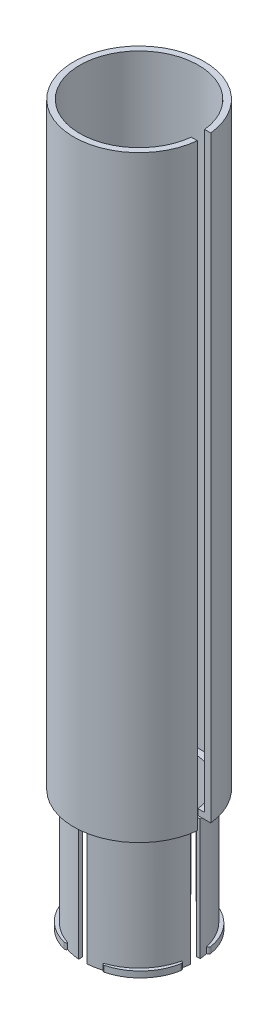
SolidWorks part; units mm, degrees
ref_plane "Front Plane" through (0, 0, 0) normal (0, 0, 1) x (1, 0, 0)
ref_plane "Top Plane" through (0, 0, 0) normal (0, 1, 0) x (1, 0, 0)
ref_plane "Right Plane" through (0, 0, 0) normal (1, 0, 0) x (0, 0, -1)
sketch "Sketch1" plane through (0, 0, 0) normal (0, 1, 0) x (1, 0, 0)
  line L5 (15.2664, 15.2664) -> (-15.2664, -15.2664) construction
  line L6 (15.2664, -15.2664) -> (-15.2664, 15.2664) construction
  circle A0 centre (0, 0) radius 21.59
  point P0 (0, 0)
  dimension "D1" = 43.18
extrude "Boss-Extrude1" add sketch "Sketch1" along normal blind 200
shell "Shell1" thickness 2
sketch "Sketch2" plane through (0, 0, 0) normal (1, 0, 0) x (0, 0, -1)
  line L0 (0, 19.558) -> (0, -19.558) construction
  line L2 (2.214, 104.2698) -> (2.214, 0)
  line L3 (2.214, 0) -> (-2.214, 0)
  line L4 (-2.214, 104.2698) -> (-2.214, 0)
  line L5 (2.214, 104.2698) -> (-2.214, 0) construction
  line L6 (2.214, 0) -> (-2.214, 104.2698) construction
  line L7 (19.558, 0) -> (-19.558, 0) construction
  line L10 (-2.214, 104.2698) -> (-2.214, 199.7944)
  line L11 (-2.214, 199.7944) -> (2.214, 199.7944)
  line L12 (2.214, 104.2698) -> (2.214, 199.7944)
  point P0 (0, 52.1349)
extrude "Cut-Extrude1" cut sketch "Sketch2" against normal mid plane 10 from offset 20
sketch "Sketch4" plane through (0, 0, 0) normal (0, -1, 0) x (1, 0, 0)
  circle A0 centre (0, 0) radius 18.651
extrude "Boss-Extrude2" add sketch "Sketch4" along normal blind 40
sketch "Sketch7" plane through (0, -40, 0) normal (0, -1, 0) x (-1, 0, 0)
  circle A0 centre (0, 0) radius 17.4097
extrude "Cut-Extrude4" cut sketch "Sketch7" against normal blind 62
sketch "Sketch8" plane through (0, 0, 0) normal (0, 1, 0) x (1, 0, 0)
  line L0 (0, -19.558) -> (0, 19.558) construction
  line L1 (-1.3929, 23.0464) -> (1.3929, 23.0464)
  line L2 (-1.3929, 23.0464) -> (-1.3929, 17.1698)
  line L3 (-1.3929, 17.1698) -> (1.3929, 17.1698)
  line L4 (1.3929, 23.0464) -> (1.3929, 17.1698)
  line L5 (-1.3929, 23.0464) -> (1.3929, 17.1698) construction
  line L6 (-1.3929, 17.1698) -> (1.3929, 23.0464) construction
  line L7 (14.2708, 1.6027) -> (23.1489, 1.6027)
  line L8 (14.2708, 1.6027) -> (14.2708, -1.6047)
  line L9 (14.2708, -1.6047) -> (23.1489, -1.6047)
  line L10 (23.1489, 1.6027) -> (23.1489, -1.6047)
  line L11 (14.2708, 1.6027) -> (23.1489, -1.6047) construction
  line L12 (14.2708, -1.6047) -> (23.1489, 1.6027) construction
  line L13 (-1.3657, -14.1994) -> (1.3929, -14.1994)
  line L14 (-1.3657, -14.1994) -> (-1.3657, -22.705)
  line L15 (-1.3657, -22.705) -> (1.3929, -22.705)
  line L16 (1.3929, -14.1994) -> (1.3929, -22.705)
  line L17 (-1.3657, -14.1994) -> (1.3929, -22.705) construction
  line L18 (-1.3657, -22.705) -> (1.3929, -14.1994) construction
  line L19 (-14.2708, 1.6027) -> (-23.1489, 1.6027)
  line L20 (-23.1489, 1.6027) -> (-23.1489, -1.6047)
  line L21 (-14.2708, -1.6047) -> (-23.1489, -1.6047)
  line L22 (-14.2708, 1.6027) -> (-14.2708, -1.6047)
  point P0 (0, 20.1081)
  point P5 (18.7098, -0.001)
  point P10 (0.0136, -18.4522)
  point P21 (0, 0)
  point P22 (0, 18.7444)
  point P23 (0, 0)
  point P24 (0, 0)
  point P25 (-1.3657, -20.4516)
  point P26 (0, 0)
  point P27 (20.2126, -1.6047)
extrude "Cut-Extrude5" cut sketch "Sketch8" against normal through all
sketch "Sketch9" plane through (0, -40, 0) normal (0, -1, 0) x (1, 0, 0)
  line L0 (23.749, 0) -> (-23.749, 0) construction
  line L2 (0, -23.749) -> (0, 23.749) construction
  arc A0 (6.5311, 17.4702) -> (18.1838, 4.8127) centre (2.5628, 2.1243) cw construction
  arc A1 (18.8328, 4.9244) -> (6.6959, 18.1077) centre (2.5628, 2.1243) ccw
  arc A2 (17.5348, 4.701) -> (6.3662, 16.8326) centre (2.5628, 2.1243) ccw
  arc A3 (17.5348, 4.701) -> (18.8328, 4.9244) centre (18.1838, 4.8127) ccw
  arc A4 (6.6959, 18.1077) -> (6.3662, 16.8326) centre (6.5311, 17.4702) ccw
  arc A5 (6.5311, -17.4702) -> (18.1838, -4.8127) centre (2.5628, -2.1243) ccw construction
  arc A6 (18.8328, -4.9244) -> (6.6959, -18.1077) centre (2.5628, -2.1243) cw
  arc A7 (17.5348, -4.701) -> (6.3662, -16.8326) centre (2.5628, -2.1243) cw
  arc A8 (17.5348, -4.701) -> (18.8328, -4.9244) centre (18.1838, -4.8127) cw
  arc A9 (6.6959, -18.1077) -> (6.3662, -16.8326) centre (6.5311, -17.4702) cw
  arc A10 (-6.5311, -17.4702) -> (-18.1838, -4.8127) centre (-2.5628, -2.1243) cw construction
  arc A11 (-18.8328, -4.9244) -> (-6.6959, -18.1077) centre (-2.5628, -2.1243) ccw
  arc A12 (-17.5348, -4.701) -> (-6.3662, -16.8326) centre (-2.5628, -2.1243) ccw
  arc A13 (-17.5348, -4.701) -> (-18.8328, -4.9244) centre (-18.1838, -4.8127) ccw
  arc A14 (-6.6959, -18.1077) -> (-6.3662, -16.8326) centre (-6.5311, -17.4702) ccw
  arc A15 (-6.5311, 17.4702) -> (-18.1838, 4.8127) centre (-2.5628, 2.1243) ccw construction
  arc A16 (-18.8328, 4.9244) -> (-6.6959, 18.1077) centre (-2.5628, 2.1243) cw
  arc A17 (-17.5348, 4.701) -> (-6.3662, 16.8326) centre (-2.5628, 2.1243) cw
  arc A18 (-17.5348, 4.701) -> (-18.8328, 4.9244) centre (-18.1838, 4.8127) cw
  arc A19 (-6.6959, 18.1077) -> (-6.3662, 16.8326) centre (-6.5311, 17.4702) cw
  arc A20 (18.5192, 2.214) -> (1.3929, 18.599) centre (0, 0) ccw construction
  point P3 (14.2242, 12.86)
  point P15 (14.2242, -12.86)
  point P23 (-14.2242, -12.86)
  point P31 (-14.2242, 12.86)
  point P36 (-6.2301, -17.5797)
  point P40 (-6.5855, 17.383)
  point P41 (-6.3662, 17.4702)
extrude "Boss-Extrude4" add sketch "Sketch9" against normal blind 2
sketch "Sketch10" plane through (0, 200, 0) normal (0, 1, 0) x (1, 0, 0)
  circle A0 centre (0, 0) radius 21.59
extrude "Cut-Extrude7" cut sketch "Sketch10" against normal mid plane 5
